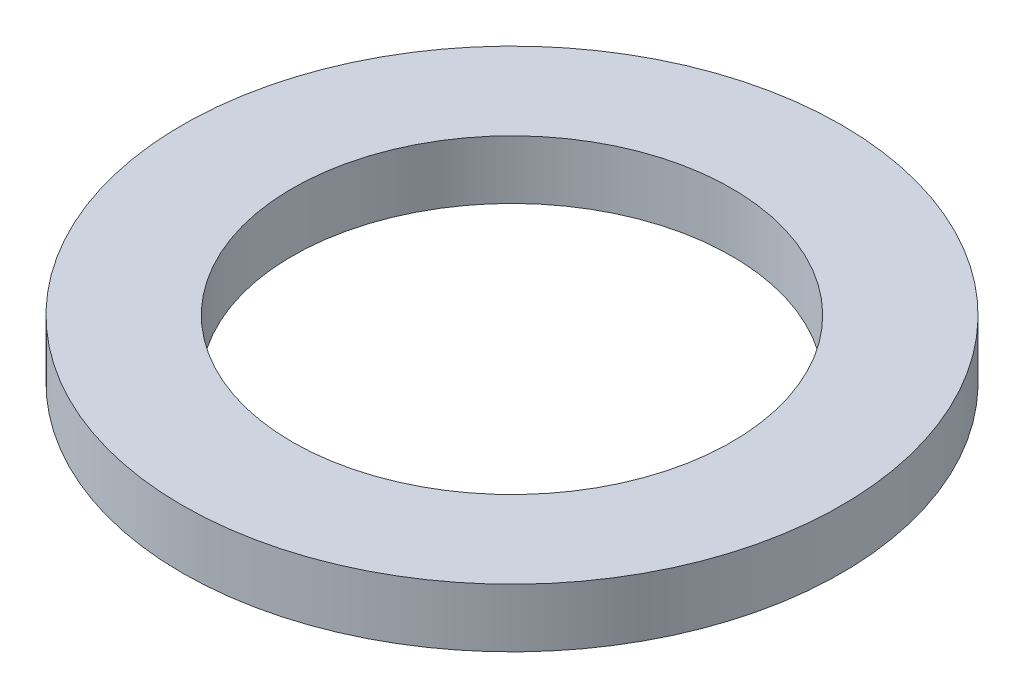
SolidWorks part; units mm, degrees
ref_plane "Front Plane" through (0, 0, 0) normal (0, 0, 1) x (1, 0, 0)
ref_plane "Top Plane" through (0, 0, 0) normal (0, 1, 0) x (1, 0, 0)
ref_plane "Right Plane" through (0, 0, 0) normal (1, 0, 0) x (0, 0, -1)
sketch "Sketch1" plane through (0, 0, 0) normal (0, 1, 0) x (1, 0, 0)
  circle A0 centre (0, 0) radius 45
  dimension "FLANGE_OD" = 90
extrude "Boss-Extrude1" add sketch "Sketch1" along normal blind 8
sketch "Sketch2" plane through (0, 0, 0) normal (0, 1, 0) x (1, 0, 0)
  circle A0 centre (0, 0) radius 30
  dimension "BORE_D" = 60
extrude "Cut-Extrude1" cut sketch "Sketch2" along normal through all
sketch "Sketch3" plane through (0, 8, 0) normal (0, 1, 0) x (1, 0, 0)
  circle A0 centre (0, 0) radius 19.6116 construction
  circle A1 centre (-19.6116, 0) radius 2.5396
  dimension "BOLT_D" = 5.0793
  dimension "BOLT_PCD" = 39.2233
extrude "Cut-Extrude2" cut sketch "Sketch3" against normal blind 7.2022 rebuild error yes
pattern_circular "CirPattern1" count 3 over 360 rebuild error yes
